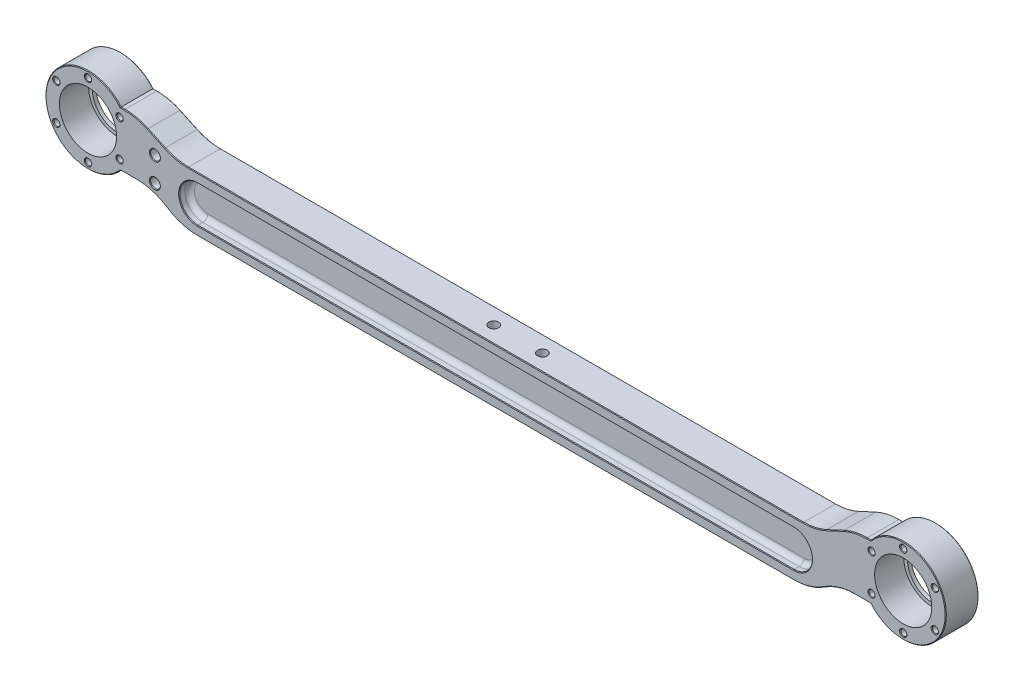
SolidWorks part; units mm, degrees
note: The reader was unsure of these and kept them because the rebuilt part matched: shared geometry of "草图6<3>", "草图6<4>".
ref_plane "前视基准面" through (0, 0, 0) normal (0, 0, 1) x (1, 0, 0)
ref_plane "上视基准面" through (0, 0, 0) normal (0, 1, 0) x (1, 0, 0)
ref_plane "右视基准面" through (0, 0, 0) normal (1, 0, 0) x (0, 0, -1)
other "Configuration Table"
sketch "草图1" plane through (0, 0, 0) normal (0, 0, 1) x (1, 0, 0)
  line L0 (0, 0) -> (0, 45) construction
  line L5 (-252.8179, 45) -> (252.8179, 45)
  line L6 (-245.2506, 0) -> (245.2506, 0)
  line L7 (335, 37.5) -> (275.0567, 37.5) construction
  line L9 (335, 37.5) -> (335, 123.9264) construction
  line L10 (285.9445, 55.7952) -> (271.8357, 49.2161)
  line L11 (308.1905, 15) -> (295, 15)
  line L12 (308.2, 60.0113) -> (304.9623, 60.0113)
  line L13 (0, 45) -> (0, 104.6772) construction
  line L14 (-335, 37.5) -> (-335, 123.9264) construction
  line L15 (-335, 37.5) -> (-275.0567, 37.5) construction
  line L16 (-308.2, 60.0113) -> (-304.9623, 60.0113)
  line L17 (-308.1905, 15) -> (-295, 15)
  line L18 (-285.9445, 55.7952) -> (-271.8357, 49.2161)
  line L19 (0, 0) -> (0, 45) construction
  arc A0 (245.2506, 0) -> (270.1253, 7.5) centre (245.2506, 45) ccw
  arc A3 (308.1905, 15) -> (308.2, 60.0113) centre (335, 37.5) ccw
  arc A6 (252.8179, 45) -> (271.8357, 49.2161) centre (252.8179, 90) ccw
  arc A8 (270.1253, 7.5) -> (295, 15) centre (295, -30) cw
  arc A9 (304.9623, 60.0113) -> (285.9445, 55.7952) centre (304.9623, 15.0113) ccw
  arc A10 (-304.9623, 60.0113) -> (-285.9445, 55.7952) centre (-304.9623, 15.0113) cw
  arc A11 (-270.1253, 7.5) -> (-295, 15) centre (-295, -30) ccw
  arc A12 (-252.8179, 45) -> (-271.8357, 49.2161) centre (-252.8179, 90) cw
  arc A13 (-308.1905, 15) -> (-308.2, 60.0113) centre (-335, 37.5) cw
  arc A14 (-245.2506, 0) -> (-270.1253, 7.5) centre (-245.2506, 45) cw
  dimension "D1" = 335
  dimension "D2" = 45
  dimension "D6" = 45
  dimension "D4" = 25
  dimension "D7" = 70
  dimension "D9" = 72.5
  dimension "D10" = 45
  dimension "D11" = 45
  dimension "D8" = 57.5
  dimension "D12" = 40.8
  dimension "D3" = 45
  dimension "D5" = 26.8
  dimension "D13" = 40
extrude "凸台-拉伸1" add sketch "草图1" along normal mid plane 27
sketch "草图2" plane through (0, 0, 13.5) normal (0, 0, 1) x (1, 0, 0)
  line L0 (-245, 22.5) -> (245, 22.5) construction
  line L1 (-245, 37.5) -> (245, 37.5)
  line L2 (-245, 7.5) -> (245, 7.5)
  line L3 (0, 0) -> (0, 45) construction
  line L4 (252.8179, 45) -> (-252.8179, 45) construction
  line L5 (335, 37.5) -> (275.0567, 37.5) construction
  arc A0 (-245, 37.5) -> (-245, 7.5) centre (-245, 22.5) ccw
  arc A1 (245, 7.5) -> (245, 37.5) centre (245, 22.5) ccw
  point P2 (0, 22.5)
  point P12 (0, 0)
  dimension "D1" = 90
extrude "切除-拉伸1" cut sketch "草图2" against normal blind 8.5
mirror "镜向1" about plane through (0, 0, 0) normal (0, 0, 1) of "切除-拉伸1"
sketch "草图3" plane through (0, 45, 0) normal (0, 1, 0) x (1, 0, 0)
  line L0 (0, 13.5) -> (0, -13.5) construction
  line L1 (252.8179, 13.5) -> (-252.8179, 13.5) construction
  line L2 (252.8179, -13.5) -> (-252.8179, -13.5) construction
  circle A0 centre (-15, 0) radius 4
  circle A1 centre (25, 0) radius 4
  point P4 (58.2259, 0)
  point P12 (0, 0)
  dimension "D1" = 15
  dimension "D2" = 40
  dimension "D3" = 8
extrude "切除-拉伸2" cut sketch "草图3" against normal blind 15
sketch "草图6" plane through (0, 0, 13.5) normal (0, 0, 1) x (1, 0, 0)
  line L0 (0, 0) -> (0, 45) construction
  line L1 (252.8179, 45) -> (-252.8179, 45) construction
  circle A0 centre (335, 37.5) radius 23.5
  arc A1 (308.1905, 15) -> (308.2, 60.0113) centre (335, 37.5) ccw construction
  circle A2 centre (335, 37.5) radius 20.5
  circle A3 centre (335, 37.5) radius 30 construction
  circle A4 centre (335, 67.5) radius 2.5
  circle A5 centre (360.9808, 52.5) radius 2.5
  circle A6 centre (360.9808, 22.5) radius 2.5
  circle A7 centre (335, 7.5) radius 2.5
  circle A8 centre (309.0192, 22.5) radius 2.5
  circle A9 centre (309.0192, 52.5) radius 2.5
  circle A10 centre (-335, 37.5) radius 30 construction
  circle A11 centre (-309.0192, 52.5) radius 2.5
  circle A12 centre (-309.0192, 22.5) radius 2.5
  circle A13 centre (-335, 7.5) radius 2.5
  circle A14 centre (-360.9808, 22.5) radius 2.5
  circle A15 centre (-360.9808, 52.5) radius 2.5
  circle A16 centre (-335, 67.5) radius 2.5
  circle A17 centre (-335, 37.5) radius 20.5
  circle A18 centre (-335, 37.5) radius 23.5
  circle A19 centre (-335, 37.5) radius 30 construction
  circle A20 centre (-309.0192, 52.5) radius 2.5
  circle A21 centre (-309.0192, 22.5) radius 2.5
  circle A22 centre (-335, 7.5) radius 2.5
  circle A23 centre (-360.9808, 22.5) radius 2.5
  circle A24 centre (-360.9808, 52.5) radius 2.5
  circle A25 centre (-335, 67.5) radius 2.5
  circle A26 centre (-335, 37.5) radius 20.5
  circle A27 centre (-335, 37.5) radius 23.5
  point P22 (335, 37.5)
  point P41 (-335, 37.5)
  point P51 (-335, 37.5)
  dimension "D1" = 47
  dimension "D2" = 41
  dimension "D3" = 60
  dimension "D4" = 5
  dimension "D5" = 6
extrude "切除-拉伸3" cut sketch "草图6" against normal blind 24 contours A0 | A18
extrude "切除-拉伸4" cut sketch "草图6<3>" against normal blind 15 contours A13 | A12 | A11 | A14 | A15 | A16 | A4 | A9 | A8 | A7 | A6 | A5
sketch "草图6<3>" plane through (0, 0, 13.5) normal (0, 0, 1) x (1, 0, 0) same geometry as "草图6"
extrude "切除-拉伸5" cut sketch "草图6<4>" against normal through all contours A17 | A2
sketch "草图6<4>" plane through (0, 0, 13.5) normal (0, 0, 1) x (1, 0, 0) same geometry as "草图6"
fillet "圆角1" radius 4 8 edges at (260, 22.5, -5) (0, 7.5, -5) (-260, 22.5, -5) (-260, 22.5, 5) (0, 37.5, 5) (260, 22.5, 5) (0, 37.5, -5) (0, 7.5, 5)
sketch "草图7" plane through (0, 0, 13.5) normal (0, 0, 1) x (1, 0, 0)
  line L0 (-335, 37.5) -> (-335, 123.9264) construction
  line L1 (-335, 37.5) -> (-275.0567, 37.5) construction
  line L2 (-245.2506, 0) -> (245.2506, 0) construction
  circle A0 centre (-280, 40) radius 4
  circle A1 centre (-280, 20) radius 4
  point P6 (0, 0)
  point P7 (0, 0)
  dimension "D1" = 8
  dimension "D2" = 55
  dimension "D3" = 2.5
  dimension "D4" = 20
extrude "切除-拉伸6" cut sketch "草图7" against normal blind 15
chamfer "倒角1" distance 0.5 angle 45 61 edges at (0, 37.5, -13.5) (260, 22.5, -13.5) (0, 7.5, -13.5) (-260, 22.5, -13.5) (0, 45, -13.5) (-262.5577, 46.0667, -13.5) (-278.8901, 52.5057, -13.5) (-295.2226, 58.9447, -13.5) (-306.5812, 60.0113, -13.5) (-370, 37.4926, -13.5) (-301.5952, 15, -13.5) (-282.0096, 13.0842, -13.5) (-258.241, 1.9158, -13.5) (0, 0, -13.5) (258.241, 1.9158, -13.5) (282.0096, 13.0842, -13.5) (301.5952, 15, -13.5) (370, 37.4926, -13.5) (306.5812, 60.0113, -13.5) (295.2226, 58.9447, -13.5) (278.8901, 52.5057, -13.5) (262.5577, 46.0667, -13.5) (311.5192, 22.5, 13.5) (311.5192, 52.5, 13.5) (337.5, 67.5, 13.5) (337.5, 7.5, 13.5) (363.4808, 22.5, 13.5) (363.4808, 52.5, 13.5) (278.8901, 52.5057, 13.5) (295.2226, 58.9447, 13.5) (306.5812, 60.0113, 13.5) (370, 37.4926, 13.5) (301.5952, 15, 13.5) (282.0096, 13.0842, 13.5) (258.241, 1.9158, 13.5) (0, 0, 13.5) (-258.241, 1.9158, 13.5) (-282.0096, 13.0842, 13.5) (-301.5952, 15, 13.5) (-370, 37.4926, 13.5) (-306.5812, 60.0113, 13.5) (-295.2226, 58.9447, 13.5) (-278.8901, 52.5057, 13.5) (-262.5577, 46.0667, 13.5) (0, 45, 13.5) (262.5577, 46.0667, 13.5) (0, 7.5, 13.5) (260, 22.5, 13.5) (0, 37.5, 13.5) (-260, 22.5, 13.5) (-337.5, 7.5, 13.5) (-311.5192, 22.5, 13.5) (-311.5192, 52.5, 13.5) (-363.4808, 22.5, 13.5) (-363.4808, 52.5, 13.5) (-337.5, 67.5, 13.5) (-276, 20, 13.5) (-276, 40, 13.5) (337.5, 7.5, -1.5) (363.4808, 22.5, -1.5) (363.4808, 52.5, -1.5)
